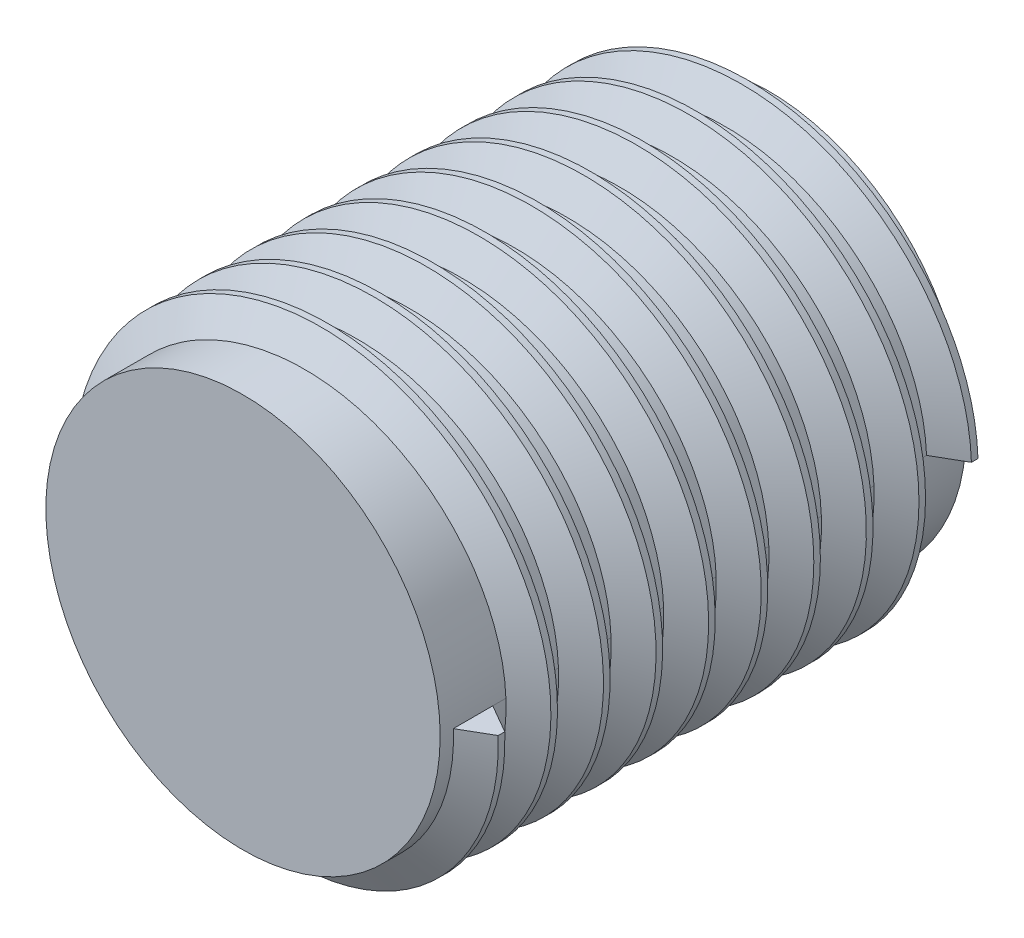
SolidWorks part; units mm, degrees
ref_plane "Front Plane" through (0, 0, 0) normal (0, 0, 1) x (1, 0, 0)
ref_plane "Top Plane" through (0, 0, 0) normal (0, 1, 0) x (1, 0, 0)
ref_plane "Right Plane" through (0, 0, 0) normal (1, 0, 0) x (0, 0, -1)
sketch "Sketch1" plane through (0, 0, 0) normal (0, 0, 1) x (1, 0, 0)
  circle A0 centre (0, 0) radius 2.3813
  dimension "D1" = 4.7625
extrude "Boss-Extrude1" add sketch "Sketch1" along normal blind 6.35
thread "Thread1" pitch 0.635 method extrude profile "Thread Profile1" start angle 0, offset 0, length 5.715, pitch 0.635, diameter 4.7625
ref_plane "Plane1" through (2.3813, 0, 0) normal (0, -1, 0) x (1, 0, 0)
sketch "Thread Profile1" plane through (2.3813, 0, 0) normal (0, -1, 0) x (1, 0, 0)
  line L0 (0, 0) -> (0, 0.635) construction
  line L1 (0, 0) -> (0.3437, 0.1984)
  line L2 (0.3437, 0.1984) -> (0.3437, 0.2778)
  line L3 (0.3437, 0.2778) -> (0, 0.4762)
  line L4 (0.3437, 0.2381) -> (0, 0.2381) construction
  line L11 (0, 0) -> (0, 0.4762)
  point P2 (0, 0)
  dimension "Pitch" = 0.635
  dimension "Profile_Angle" = 60
  dimension "Profile_Land" = 0.0794
  dimension "Profile_Height" = 0.3437
